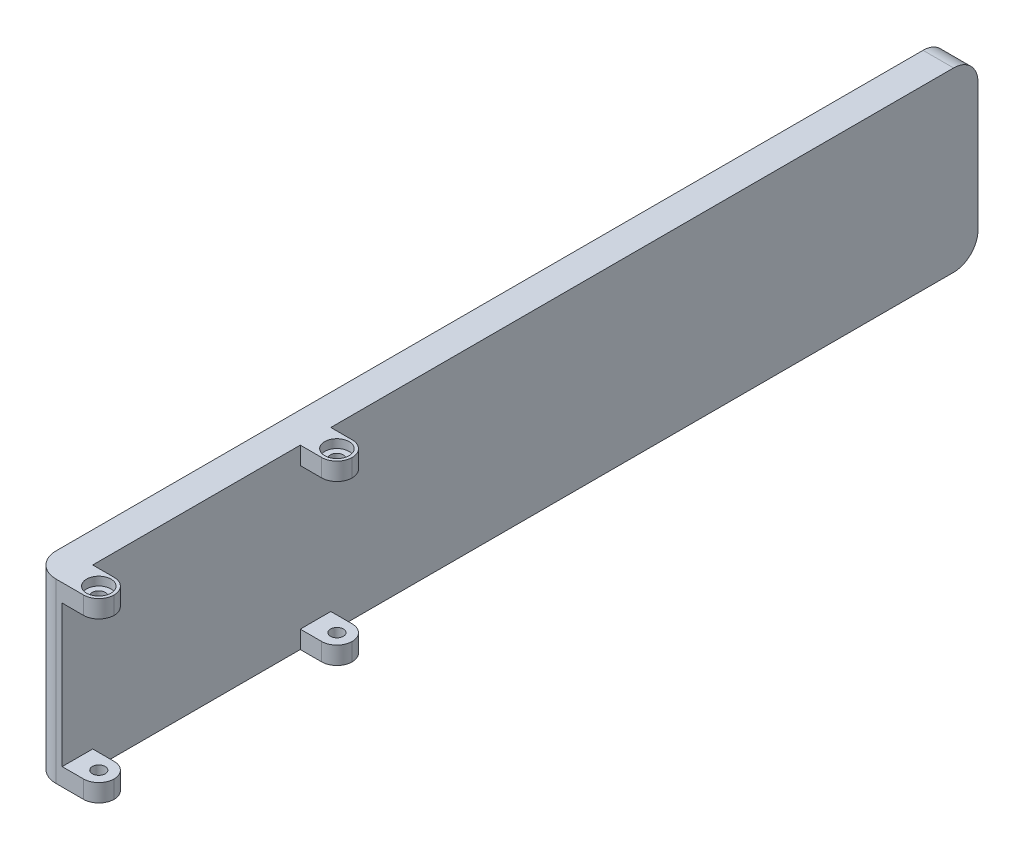
SolidWorks part; units mm, degrees
material "Esun Hard Tough Resin"
ref_plane "Front Plane" through (0, 0, 0) normal (0, 0, 1) x (1, 0, 0)
ref_plane "Top Plane" through (0, 0, 0) normal (0, 1, 0) x (1, 0, 0)
ref_plane "Right Plane" through (0, 0, 0) normal (1, 0, 0) x (0, 0, -1)
sketch "Sketch1" plane through (0, 0, 0) normal (0, 1, 0) x (1, 0, 0)
  line L1 (0, 0) -> (-5, 0)
  line L2 (0, 0) -> (0, 150)
  line L3 (0, 150) -> (-5, 150)
  line L4 (-5, 0) -> (-5, 150)
  dimension "D1" = 5
  dimension "D2" = 150
extrude "Boss-Extrude1" add sketch "Sketch1" along normal blind 29
sketch "Sketch2" plane through (0, 0, 0) normal (1, 0, 0) x (0, 0, -1)
  line L0 (0, 29) -> (150, 29) construction
  line L1 (0, 29) -> (5, 29)
  line L2 (0, 29) -> (0, 26.1)
  line L3 (0, 26.1) -> (5, 26.1)
  line L4 (5, 29) -> (5, 26.1)
  line L5 (39, 29) -> (44, 29)
  line L6 (39, 29) -> (39, 26.1)
  line L7 (39, 26.1) -> (44, 26.1)
  line L8 (44, 29) -> (44, 26.1)
  line L9 (-1000, 14.5) -> (49000, 14.5) construction
  line L10 (0, 29) -> (0, 0) construction
  line L11 (39, 2.9) -> (44, 2.9)
  line L12 (44, 0) -> (44, 2.9)
  line L13 (39, 0) -> (44, 0)
  line L14 (39, 0) -> (39, 2.9)
  line L15 (0, 2.9) -> (5, 2.9)
  line L16 (5, 0) -> (5, 2.9)
  line L17 (0, 0) -> (5, 0)
  line L18 (0, 0) -> (0, 2.9)
  point P12 (2.5, 26.1)
  point P16 (0, 14.5)
  point P17 (41.5, 26.1)
  dimension "D1" = 39
  dimension "D2" = 5
  dimension "D3" = 2.9
extrude "Boss-Extrude2" add sketch "Sketch2" along normal blind 6
sketch "Sketch3" plane through (0, 29, 0) normal (0, 1, 0) x (1, 0, 0)
  line L0 (6, 44) -> (6, 39) construction
  line L1 (6, 44) -> (6, 39) construction
  circle A0 centre (3.5, 41.5) radius 1.05
  circle A1 centre (3.5, 2.5) radius 1.05
  point P8 (6, 41.5)
  dimension "D1" = 2.1
  dimension "D2" = 39
  dimension "D3" = 2.5
extrude "Cut-Extrude1" cut sketch "Sketch3" against normal through all
sketch "Sketch4" plane through (0, 29, 0) normal (0, 1, 0) x (1, 0, 0)
  circle A0 centre (3.5, 2.5) radius 1.05 construction
  circle A1 centre (3.5, 41.5) radius 1.05 construction
  circle A2 centre (3.5, 2.5) radius 1.05 construction
  circle A3 centre (3.5, 41.5) radius 1.05 construction
  circle A4 centre (3.5, 41.5) radius 2
  circle A5 centre (3.5, 2.5) radius 2
  dimension "D1" = 4
extrude "Cut-Extrude2" cut sketch "Sketch4" against normal blind 1.4
ref_plane "Plane1" through (0, 14.5, 0) normal (0, 1, 0) x (1, 0, 0)
mirror "Mirror2" about plane through (0, 14.5, 0) normal (0, 1, 0) of "Cut-Extrude2"
fillet "Fillet1" radius 4 3 edges at (-2.5, 0, -150) (-2.5, 29, -150) (-5, 14.5, 0)
fillet "Fillet2" radius 2.5 8 edges at (6, 1.45, -5) (6, 1.45, 0) (6, 1.45, -44) (6, 1.45, -39) (6, 27.55, -44) (6, 27.55, -39) (6, 27.55, -5) (6, 27.55, 0)
